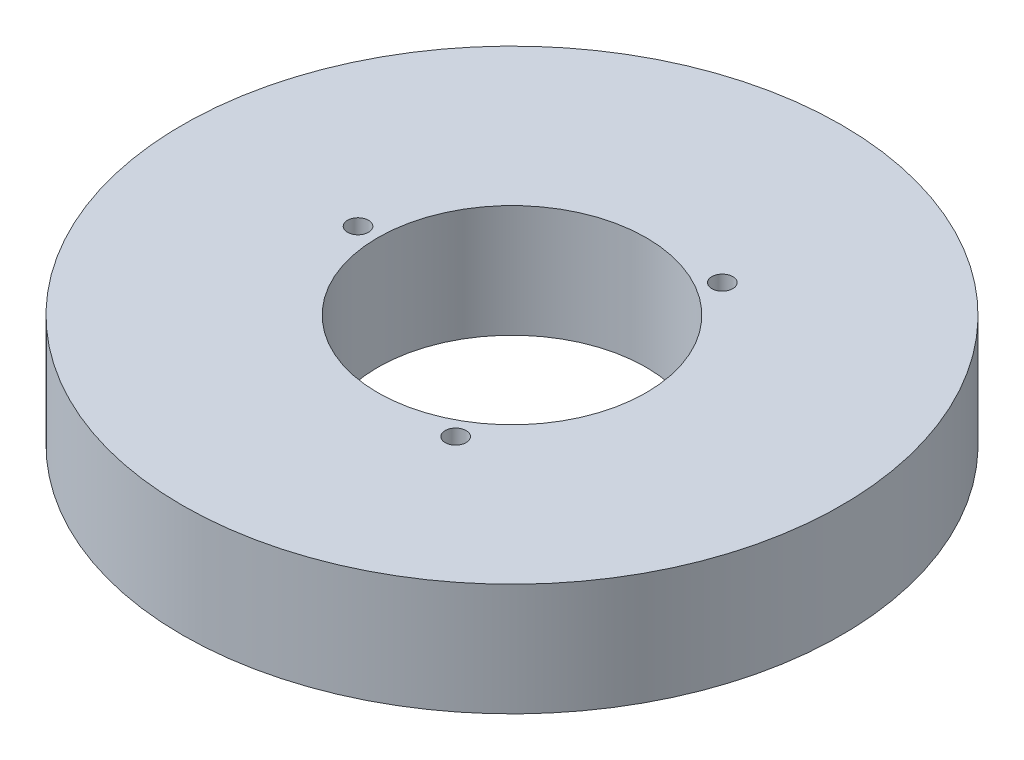
SolidWorks part; units mm, degrees
ref_plane "Front Plane" through (0, 0, 0) normal (0, 0, 1) x (1, 0, 0)
ref_plane "Top Plane" through (0, 0, 0) normal (0, 1, 0) x (1, 0, 0)
ref_plane "Right Plane" through (0, 0, 0) normal (1, 0, 0) x (0, 0, -1)
sketch "Sketch1" plane through (0, 0, 0) normal (0, 1, 0) x (1, 0, 0)
  circle A0 centre (0, 0) radius 67.5
  dimension "FLANGE_OD" = 135
extrude "Boss-Extrude1" add sketch "Sketch1" along normal blind 23
sketch "Sketch2" plane through (0, 0, 0) normal (0, 1, 0) x (1, 0, 0)
  circle A0 centre (0, 0) radius 27.5
  dimension "BORE_D" = 55
extrude "Cut-Extrude1" cut sketch "Sketch2" along normal through all
sketch "Sketch3" plane through (0, 23, 0) normal (0, 1, 0) x (1, 0, 0)
  circle A0 centre (0, 0) radius 31.534 construction
  circle A1 centre (-31.534, 0) radius 2.1473
  dimension "BOLT_D" = 4.2947
  dimension "BOLT_PCD" = 63.068
extrude "Cut-Extrude2" cut sketch "Sketch3" against normal blind 14.339
pattern_circular "CirPattern1" count 3 over 360 about axis through (0, 0, 0) along (0, 1, 0) of "Cut-Extrude2"
